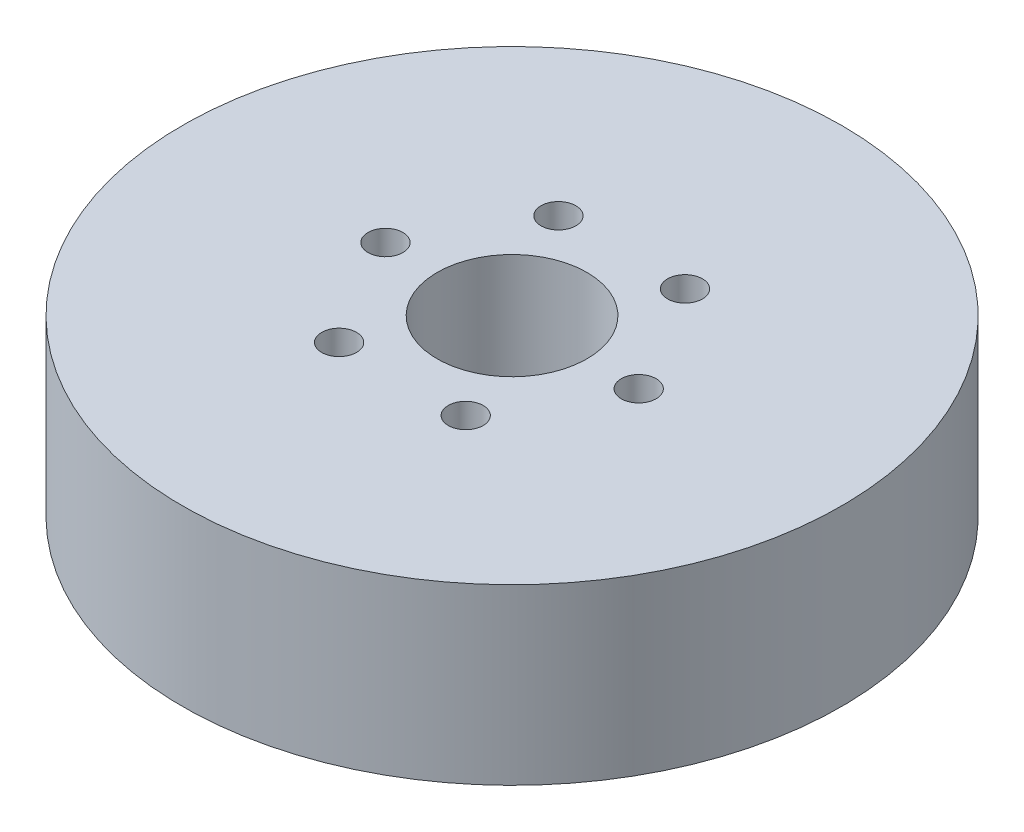
SolidWorks part; units mm, degrees
ref_plane "Front Plane" through (0, 0, 0) normal (0, 0, 1) x (1, 0, 0)
ref_plane "Top Plane" through (0, 0, 0) normal (0, 1, 0) x (1, 0, 0)
ref_plane "Right Plane" through (0, 0, 0) normal (1, 0, 0) x (0, 0, -1)
sketch "Sketch1" plane through (0, 0, 0) normal (0, 1, 0) x (1, 0, 0)
  circle A0 centre (0, 0) radius 55
  dimension "FLANGE_OD" = 110
extrude "Boss-Extrude1" add sketch "Sketch1" along normal blind 29
sketch "Sketch2" plane through (0, 0, 0) normal (0, 1, 0) x (1, 0, 0)
  circle A0 centre (0, 0) radius 12.5
  dimension "BORE_D" = 25
extrude "Cut-Extrude1" cut sketch "Sketch2" along normal through all
sketch "Sketch3" plane through (0, 29, 0) normal (0, 1, 0) x (1, 0, 0)
  circle A0 centre (0, 0) radius 21.1302 construction
  circle A1 centre (-21.1302, 0) radius 2.9107
  dimension "BOLT_D" = 5.8214
  dimension "BOLT_PCD" = 42.2603
extrude "Cut-Extrude2" cut sketch "Sketch3" against normal blind 25.916
pattern_circular "CirPattern1" count 6 over 360 about axis through (0, 0, 0) along (0, 1, 0) of "Cut-Extrude2"
